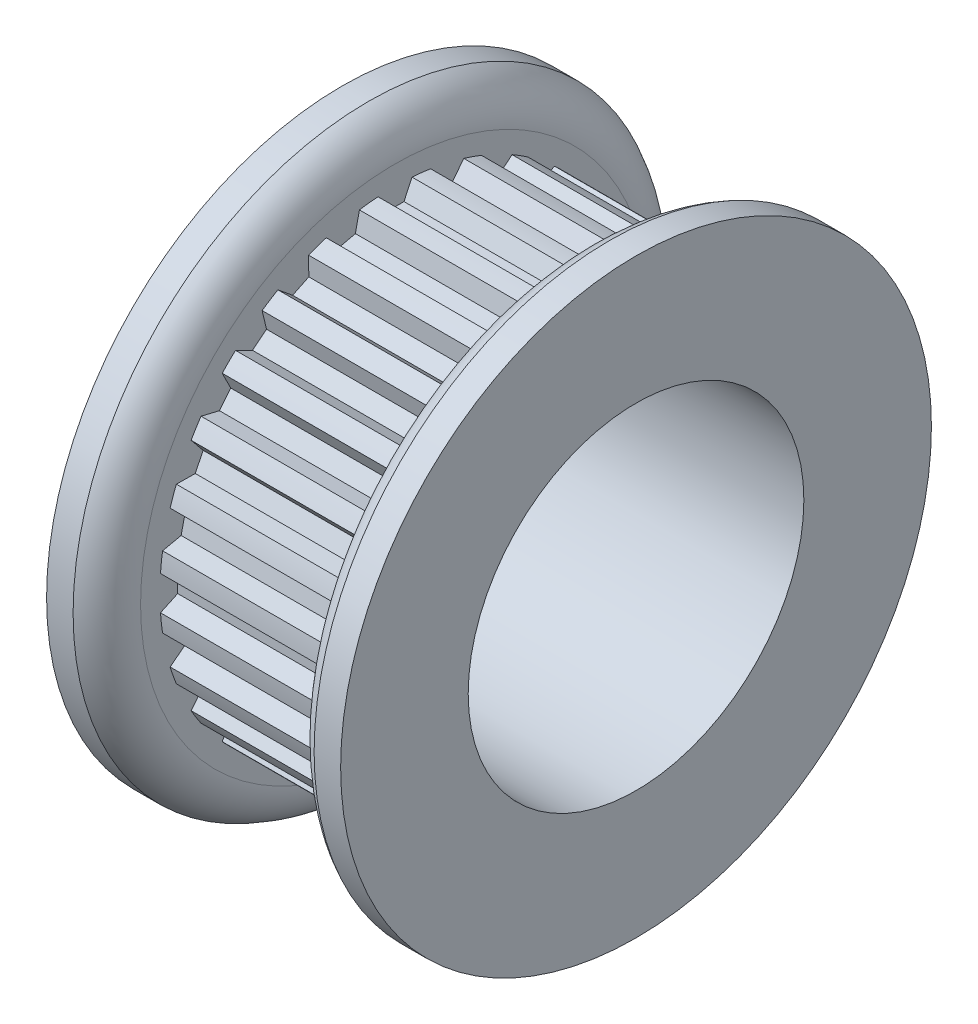
SolidWorks part; units mm, degrees
ref_plane "Front Plane" through (0, 0, 0) normal (0, 0, 1) x (1, 0, 0)
ref_plane "Top Plane" through (0, 0, 0) normal (0, 1, 0) x (1, 0, 0)
ref_plane "Right Plane" through (0, 0, 0) normal (1, 0, 0) x (0, 0, -1)
sketch "Sketch2" plane through (0, 0, 0) normal (1, 0, 0) x (0, 0, -1)
  line L3 (0, 0) -> (0, 8.2296) construction
  line L6 (0, -8.7376) -> (0, -9.0551) construction
  line L7 (-0.5715, 8.7189) -> (-0.3401, 8.2226)
  line L8 (0.5715, 8.7189) -> (0.3401, 8.2226)
  line L9 (-0.5715, 8.7189) -> (-0.6434, 8.8731)
  line L10 (0.5715, 8.7189) -> (0.6434, 8.8731)
  line L12 (-0.3401, 8.2226) -> (0.3401, 8.2226)
  line L14 (0, 8.7376) -> (0, 9.0551) construction
  line L15 (0, 0) -> (0, -1.143) construction
  circle A0 centre (0, 0) radius 9.0551 construction
  circle A1 centre (0, 0) radius 8.2296 construction
  circle A2 centre (0, 0) radius 8.7376 construction
  arc A7 (0.6434, 8.8731) -> (-0.6434, 8.8731) centre (0, 0) ccw
  point P5 (0, 8.8963)
  dimension "D3" = 0.3175
  dimension "D1" = 50
sketch "Sketch1" plane through (0, 0, 0) normal (0, 0, 1) x (1, 0, 0)
  line L0 (-8.7376, 0) -> (8.7376, 0) construction
  line L1 (-8.7376, 3.175) -> (8.7376, 3.175)
  line L2 (-8.7376, 3.175) -> (-8.7376, 8.7376)
  line L3 (-2.3876, 11.176) -> (-1.3843, 11.176)
  line L4 (-0.381, 9.0551) -> (-0.381, 9.6266)
  line L5 (-0.381, 10.1981) -> (-0.381, 9.0551) construction
  line L6 (-0.381, 9.0551) -> (6.731, 9.0551)
  line L7 (6.731, 9.0551) -> (6.731, 9.6266)
  line L8 (6.731, 9.0551) -> (8.7376, 9.0551) construction
  line L9 (7.7343, 11.176) -> (8.7376, 11.176)
  line L10 (8.7376, 11.176) -> (8.7376, 3.175)
  line L11 (7.7343, 9.0551) -> (7.7343, 11.176) construction
  line L12 (-5.5626, 8.7376) -> (-5.5626, 3.175) construction
  line L13 (-2.3876, 11.176) -> (-2.3876, 8.7376)
  line L14 (-2.3876, 8.7376) -> (-8.7376, 8.7376)
  arc A0 (6.731, 9.6266) -> (7.7343, 11.176) centre (8.429, 9.6266) cw
  arc A1 (-0.381, 9.6266) -> (-1.3843, 11.176) centre (-2.079, 9.6266) ccw
  dimension "Bore Size" = 6.35
  dimension "Overall Width" = 17.4752
  dimension "Inside Width" = 7.112
  dimension "OD" = 22.352
  dimension "D2" = 18.1102
  dimension "D3" = 1.143
  dimension "D4" = 0.5715
  dimension "Outside Width" = 11.1252
revolve "Revolve1" add sketch "Sketch1" angle 360 mid plane about L0
sketch "Sketch4" plane through (-0.381, 0, 0) normal (1, 0, 0) x (0, 0, -1)
  circle A0 centre (0, 0) radius 8.8963
  circle A2 centre (0, 0) radius 9.0551
  circle A3 centre (0, 0) radius 9.0551 construction
extrude "Cut-Extrude2" cut sketch "Sketch4" along normal up to surface (7.112 mm away) up to face at (6.731, 0, 9.0551)
sketch "Sketch3" plane through (-0.381, 0, 0) normal (1, 0, 0) x (0, 0, -1)
  line L2 (-0.5715, 8.7189) -> (-0.3401, 8.2226) construction
  line L3 (-0.3401, 8.2226) -> (0.3401, 8.2226) construction
  line L4 (0.5715, 8.7189) -> (0.3401, 8.2226) construction
  line L5 (-0.6434, 8.8731) -> (-0.3401, 8.2226)
  line L6 (-0.3401, 8.2226) -> (0.3401, 8.2226)
  line L7 (0.6434, 8.8731) -> (0.3401, 8.2226)
  arc A1 (0.6434, 8.8731) -> (-0.6434, 8.8731) centre (0, 0) ccw construction
  arc A2 (0.6434, 8.8731) -> (-0.6434, 8.8731) centre (0, 0) ccw
extrude "Cut-Extrude1" cut sketch "Sketch3" along normal up to surface (7.112 mm away)
pattern_circular "CirPattern1" count 28 over 360 of "Cut-Extrude1"
sketch "Sketch5" plane through (0, 0, 0) normal (0, 0, 1) x (1, 0, 0)
  line L1 (6.731, 9.6266) -> (6.731, -9.6266) construction
  point P0 (6.731, 0)
sketch "Sketch6" plane through (-8.7376, 0, 0) normal (-1, 0, 0) x (0, 0, 1)
  circle A0 centre (0, 0) radius 6.35
  dimension "D1" = 12.7
extrude "Cut-Extrude3" cut sketch "Sketch6" against normal through all
split "Split1" bodies to split 110 resulting bodies 111 split by face at (-2.3876, 0, 8.7376)
equation "\"D3@Sketch2\" = (\"hs@Sketch2\"-\"ht@Sketch2\")/2"
equation "\"D2@Sketch1\" = \"PD@Sketch2\""
equation "\"D3@Sketch1\" = \"hs@Sketch2\""
equation "\"D4@Sketch1\" = \"D3@Sketch1\"/2"
